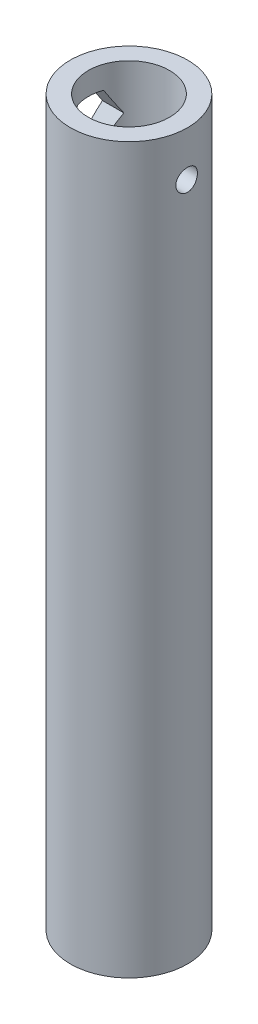
SolidWorks part; units mm, degrees
ref_plane "Front Plane" through (0, 0, 0) normal (0, 0, 1) x (1, 0, 0)
ref_plane "Top Plane" through (0, 0, 0) normal (0, 1, 0) x (1, 0, 0)
ref_plane "Right Plane" through (0, 0, 0) normal (1, 0, 0) x (0, 0, -1)
sketch "Sketch1" plane through (0, 0, 0) normal (0, 1, 0) x (1, 0, 0)
  circle A0 centre (0, 0) radius 5.715
  circle A1 centre (0, 0) radius 8.255
  dimension "D1" = 11.43
  dimension "D2" = 16.51
extrude "Boss-Extrude1" add sketch "Sketch1" along normal blind 101.981
sketch "Sketch2" plane through (0, 0, 0) normal (1, 0, 0) x (0, 0, -1)
  line L0 (-8.255, 101.981) -> (8.255, 101.981) construction
  line L1 (1.8331, 92.456) -> (3.6662, 95.631)
  line L2 (3.6662, 95.631) -> (1.8331, 98.806)
  line L3 (1.8331, 98.806) -> (-1.8331, 98.806)
  line L4 (-1.8331, 98.806) -> (-3.6662, 95.631)
  line L5 (-3.6662, 95.631) -> (-1.8331, 92.456)
  line L6 (-1.8331, 92.456) -> (1.8331, 92.456)
  line L7 (8.255, 101.981) -> (-8.255, 101.981) construction
  line L8 (-8.255, 101.981) -> (-8.255, 0) construction
  circle A0 centre (0, 95.631) radius 3.175 construction
  point P1 (0, 101.981)
  dimension "D1" = 6.35
  dimension "D2" = 6.35
extrude "Cut-Extrude1" cut sketch "Sketch2" against normal through all
sketch "Sketch3" plane through (0, 0, 0) normal (1, 0, 0) x (0, 0, -1)
  line L0 (5.715, 101.981) -> (-5.715, 101.981) construction
  line L1 (-8.255, 101.981) -> (8.255, 101.981) construction
  line L2 (8.255, 101.981) -> (-8.255, 101.981) construction
  line L3 (8.255, 0) -> (8.255, 101.981) construction
  circle A0 centre (0, 95.631) radius 1.524
  point P15 (0, 101.981)
  dimension "D2" = 3.048
  dimension "D1" = 6.35
extrude "Cut-Extrude2" cut sketch "Sketch3" along normal through all
sketch "Sketch4" plane through (0, 0, 0) normal (0, -1, 0) x (1, 0, 0)
  circle A0 centre (0, 0) radius 5.715
  circle A1 centre (0, 0) radius 5.08
  circle A2 centre (0, 0) radius 5.715 construction
  dimension "D1" = 10.16
extrude "Boss-Extrude2" add sketch "Sketch4" against normal blind 3.81
